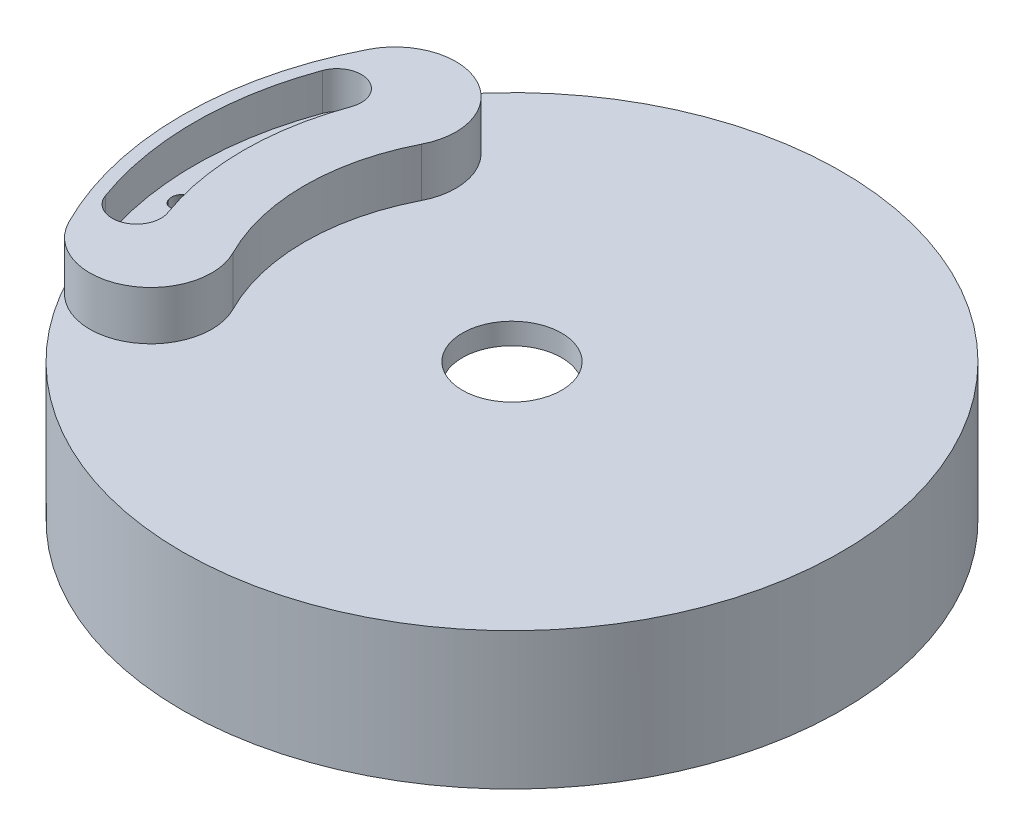
SolidWorks part; units mm, degrees
note: '?' marks a value the reader was unsure of.
material "1023 Carbon Steel Sheet (SS)"
ref_plane "Front Plane" through (0, 0, 0) normal (0, 0, 1) x (1, 0, 0)
ref_plane "Top Plane" through (0, 0, 0) normal (0, 1, 0) x (1, 0, 0)
ref_plane "Right Plane" through (0, 0, 0) normal (1, 0, 0) x (0, 0, -1)
ref_axis "Axis1" through (0, 17.78, 0) along (0, -1, 0)?
sketch "Sketch9" plane through (0, 0, 0) normal (0, 0, 1) x (1, 0, 0)
  line L0 (-10.16, 10.16) -> (-10.16, 24.525)
  line L1 (-10.16, 24.525) -> (-67.5, 24.525)
  line L2 (-67.5, 24.525) -> (-67.5, -13.575)
  line L3 (-67.5, -13.575) -> (-63.375, -13.575)
  line L4 (-63.375, -13.575) -> (-63.375, 10.795)
  line L5 (-63.375, 10.795) -> (-53.825, 10.795)
  line L6 (-53.825, 10.795) -> (-53.825, 5.08)
  line L10 (0, 18.1217) -> (0, -20.6688) construction
  line L11 (-53.825, 5.08) -> (-46, 5.08)
  line L12 (-46, 5.08) -> (-46, 6.35)
  line L13 (-46, 6.35) -> (-36, 6.35)
  line L14 (-36, 6.35) -> (-36, 7.62)
  line L15 (-36, 7.62) -> (-21, 7.62)
  line L16 (-21, 7.62) -> (-21, 10.16)
  line L17 (-21, 10.16) -> (-10.16, 10.16)
  line L18 (-63.375, 9.525) -> (0, 9.525) construction
  line L19 (-63.375, 0) -> (0, 0) construction
  dimension "D1" = 20.32
  dimension "D2" = 135
  dimension "D5" = 38.1
  dimension "D6" = 126.75
  dimension "D3" = 9.525
  dimension "D4" = 5.08
  dimension "D8" = 46
  dimension "D9" = 6.35
  dimension "D10" = 36
  dimension "D11" = 7.62
  dimension "D12" = 21
  dimension "D13" = 10.16
  dimension "D7" = 53.825
  dimension "D15" = 15
  dimension "D14" = 1.27
revolve "Revolve1" add sketch "Sketch9" angle 360 about L10
sketch "Sketch1" plane through (0, 24.525, 0) normal (0, 1, 0) x (1, 0, 0)
  circle A1 centre (0, 0) radius 67.5 construction
  circle A2 centre (0, 0) radius 67.5
  arc A3 (-37.8558, 19.3182) -> (-37.8558, -19.3182) centre (0, 0) ccw
  arc A4 (-37.8558, 19.3182) -> (-60.1238, 30.6818) centre (-48.9898, 25) ccw
  arc A5 (-37.8558, -19.3182) -> (-60.1238, -30.6818) centre (-48.9898, -25) cw
  dimension "D1" = 25
  dimension "D2" = 50
extrude "Gear Slot" cut sketch "Sketch1" against normal blind 10
ref_plane "Plane2" through (-60, 0, 0) normal (1, 0, 0) x (0, 0, -1)
sketch "Sketch10" plane through (0, 24.525, 0) normal (0, 1, 0) x (1, 0, 0)
  line L0 (0, 0) -> (-56.3816, 20.5212) construction
  line L1 (0, 0) -> (-56.3816, -20.5212) construction
  arc A0 (-51.6831, -18.8111) -> (-51.6831, 18.8111) centre (0, 0) cw
  arc A1 (-61.08, -22.2313) -> (-61.08, 22.2313) centre (0, 0) cw
  arc A2 (-56.3816, -20.5212) -> (-56.3816, 20.5212) centre (0, 0) cw construction
  arc A3 (-61.08, 22.2313) -> (-51.6831, 18.8111) centre (-56.3816, 20.5212) cw
  arc A4 (-51.6831, -18.8111) -> (-61.08, -22.2313) centre (-56.3816, -20.5212) cw
  point P9 (-65, 0)
  dimension "D1" = 60
  dimension "D2" = 10
  dimension "D3" = 40
sketch "Sketch5" plane through (-60, 0, 0) normal (1, 0, 0) x (0, 0, -1)
  line L0 (-7.2694, 3.4576) -> (-9.7781, 16.3641)
  line L1 (-9.7781, 16.3641) -> (-12.0051, 20.9299)
  line L2 (-12.0051, 20.9299) -> (-9.102, 22.3459)
  line L3 (-9.102, 22.3459) -> (-6.875, 17.78)
  line L4 (-6.875, 17.78) -> (1.7508, 7.8571)
  line L5 (1.7508, 7.8571) -> (-7.2694, 3.4576)
  line L6 (-2.7593, 5.6573) -> (-10.5535, 21.6379)
  line L7 (-9.7781, 16.3641) -> (-6.875, 17.78) construction
  line L8 (-2.7593, 5.6573) -> (-2.7593, 23.2756) construction
  line L9 (-2.7593, 5.6573) -> (0, 0) construction
  dimension "D2" = 15
  dimension "D3" = 3.23
  dimension "D5" = 12.7
  dimension "D6" = 5.08
  dimension "D1" = 26
  dimension "D4" = 17.78
revolve "Orifice" cut sketch "Sketch5" angle 360 about L6
pattern_circular "CirPattern1" count 2 every 10 about axis through (0, 17.78, 0) along (0, -1, 0) of "Orifice"
sketch "Stock Sketch" plane through (0, 24.525, 0) normal (0, 1, 0) x (1, 0, 0)
  circle A0 centre (0, 0) radius 88.9
  dimension "D1" = 177.8
extrude "Gas Manifold" cut sketch "Sketch10" against normal blind 7.62
ref_plane "Plane3" through (0, 0, 0) normal (0, -1, 0) x (-1, 0, 0)
equation "\"D3@Sketch5\"=\"nozzle diameter@[TP] [Turb] Turbine.Assembly\""
equation "\"D6@Sketch9\"=2*(\"rotor tip@[TP] [Turb] Turbine.Assembly\"+\"rotor clearance@[TP] [Turb] Turbine.Assembly\")"
equation "\"D7@Sketch9\"=\"rotor base@[TP] [Turb] Turbine.Assembly\"-3"
equation "\"D1@Sketch10\"=\"rotor pitchline@[TP] [Turb] Turbine.Assembly\""
